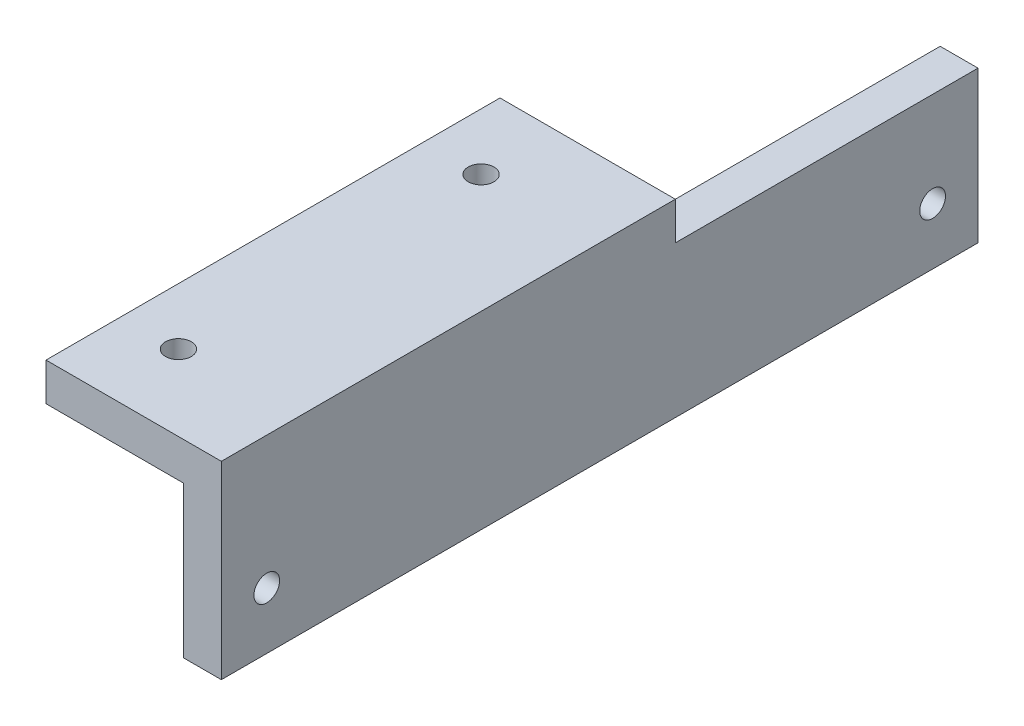
SolidWorks part; units mm, degrees
ref_plane "Front" through (0, 0, 0) normal (0, 0, 1) x (1, 0, 0)
ref_plane "Top" through (0, 0, 0) normal (0, 1, 0) x (1, 0, 0)
ref_plane "Right" through (0, 0, 0) normal (1, 0, 0) x (0, 0, -1)
sketch "Sketch1" plane through (0, 0, 0) normal (1, 0, 0) x (0, 0, -1)
  line L0 (50, 20) -> (50, 0)
  line L1 (0, 0) -> (100, 0)
  line L2 (0, 0) -> (0, 20)
  line L3 (0, 20) -> (100, 20)
  line L4 (100, 0) -> (100, 20)
  line L5 (6, 7.5) -> (94, 7.5)
  line L7 (9.2332, 7.5) -> (7.6166, 10.3)
  line L8 (7.6166, 10.3) -> (4.3834, 10.3)
  line L9 (4.3834, 10.3) -> (2.7668, 7.5)
  line L10 (2.7668, 7.5) -> (4.3834, 4.7)
  line L11 (4.3834, 4.7) -> (7.6166, 4.7)
  line L12 (7.6166, 4.7) -> (9.2332, 7.5)
  line L13 (97.2332, 7.5) -> (95.6166, 10.3)
  line L14 (95.6166, 10.3) -> (92.3834, 10.3)
  line L15 (92.3834, 10.3) -> (90.7668, 7.5)
  line L16 (90.7668, 7.5) -> (92.3834, 4.7)
  line L17 (92.3834, 4.7) -> (95.6166, 4.7)
  line L18 (95.6166, 4.7) -> (97.2332, 7.5)
  circle A0 centre (6, 7.5) radius 1.7
  circle A1 centre (94, 7.5) radius 1.7
  circle A2 centre (6, 7.5) radius 2.8 construction
  circle A3 centre (94, 7.5) radius 2.8 construction
  point P10 (50, 10)
  point P12 (50, 7.5)
  dimension "D4" = 7.5
  dimension "D1" = 20
  dimension "D2" = 100
  dimension "D3" = 88
  dimension "D5" = 0
extrude "Boss-Extrude1" add sketch "Sketch1" along normal blind 2.5 contours A0 L0 L3 L2 L1 | A1 L0 L1 L4 L3 | A0 L7 L8 L9 L10 L11 L12 | A1 L16 L17 L18 L13 L14 L15 region at (0, 8.8572, -91.6492) region at (0, 10.0698, -74.4696) region at (0, 6.1428, -8.3508) region at (0, 10.0698, -25.5304)
extrude "Boss-Extrude2" add sketch "Sketch1<3>" against normal blind 2.5 contours L12 L11 L10 L9 L8 L7 L0 L3 L2 L1 | L18 L17 L16 L0 L1 L4 L3 L15 L14 L13 region at (0, 10.0698, -74.4696) region at (0, 10.0698, -25.5304)
sketch "Sketch1<3>" plane through (0, 0, 0) normal (1, 0, 0) x (0, 0, -1) same geometry as "Sketch1"
sketch "Sketch2" plane through (0, 20, 0) normal (0, 1, 0) x (1, 0, 0)
  line L0 (2.5, 0) -> (2.5, 100)
  line L1 (2.5, 0) -> (-20.675, 0)
  line L2 (2.5, 100) -> (-20.675, 100)
  line L3 (-20.675, 0) -> (-20.675, 100)
  line L4 (-2.5, 0) -> (-2.5, 100) construction
  line L5 (-13.175, 0) -> (-13.175, 100)
  line L6 (-20.675, 15) -> (-2.5, 15)
  line L7 (-13.175, 10) -> (-13.175, 90)
  line L8 (-2.5, 15) -> (2.5, 15)
  line L9 (2.5, 15) -> (2.5, 100)
  line L10 (-20.675, 60) -> (2.5, 60)
  circle A0 centre (-13.175, 10) radius 1.7
  circle A1 centre (-13.175, 90) radius 1.7
  circle A2 centre (-13.175, 50) radius 1.7
  point P15 (-13.175, 50)
  line M7 (-2.5, 100) -> (-2.5, 0)
  line M8 (-2.5, 0) -> (2.5, 0)
  line M9 (2.5, 0) -> (2.5, 100)
  dimension "D6" = 40
  dimension "D7" = 10
  dimension "D1" = 7.5
  dimension "D2" = 18.175
  dimension "D3" = 15
  dimension "D4" = 50
  dimension "D5" = 10
extrude "Boss-Extrude3" add sketch "Sketch2" along normal blind 5 contours A2 L5 L6 L10 M7 | A2 L5 L10 L3 L6 | A0 L7 L6 L3 L1 L5 | A0 L5 L1 L6 L7 M7 | L8 M7 M8 M9 | L10 L8 L0 M7 region at (0, 20, -7.5) region at (0, 20, -37.5) region at (-7.7028, 20, -7.4271) region at (-7.7935, 20, -37.3807) region at (-17.0523, 20, -7.3949) region at (-16.9663, 20, -37.3296)
ref_plane "Plane1" [suppressed] through (2.5, 20, -15) normal (1, 0, 0) x (0, 0, -1)
sketch "Sketch3" [suppressed] plane through (2.5, 20, -15) normal (1, 0, 0) x (0, 0, -1)
  line L0 (0, 0) -> (0, 30)
  line L1 (0, 30) -> (5, 30)
  line L2 (5, 30) -> (5, 0)
  line L3 (5, 0) -> (0, 0)
  dimension "D1" = 30
  dimension "D2" = 5
extrude "Boss-Extrude4" [suppressed] add sketch "Sketch3" against normal up to vertex
fillet "Fillet1" [suppressed] radius 10
sketch "Sketch4" [suppressed] plane through (0, 0, -20) normal (0, 0, -1) x (-1, 0, 0)
  line L0 (13.175, 50) -> (13.175, 30)
  line L1 (20.675, 50) -> (-2.5, 50) construction
  line L2 (-2.5, 30) -> (20.675, 30) construction
  line L3 (20.675, 30) -> (20.675, 50) construction
  circle A0 centre (13.175, 45) radius 1.7
  circle A1 centre (13.175, 35) radius 1.7
  dimension "D4" = 3.4
  dimension "D5" = 3.4
  dimension "D1" = 7.5
  dimension "D2" = 5
  dimension "D3" = 5
extrude "Cut-Extrude1" [suppressed] cut sketch "Sketch4" against normal blind 23 contours L0 A0 | L0 A0 | L0 A1 | L0 A1
